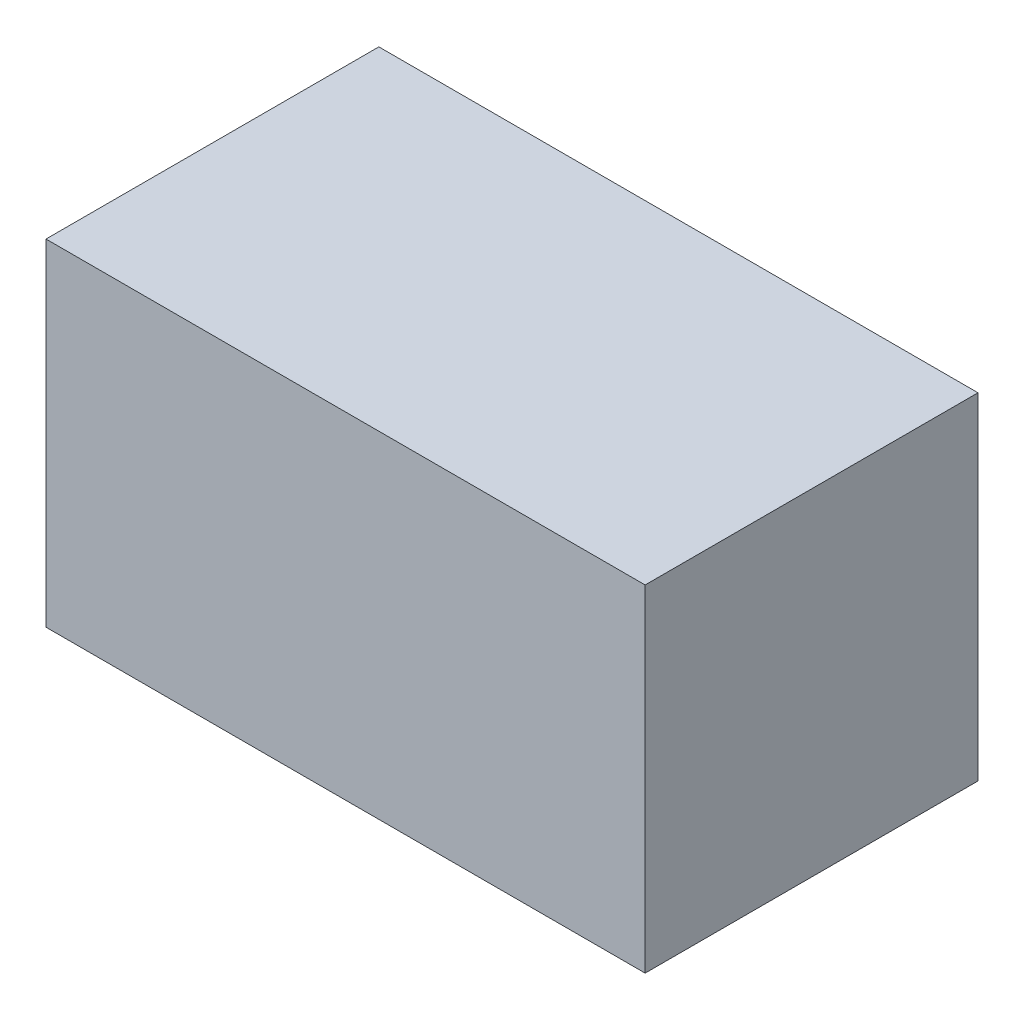
SolidWorks part; units mm, degrees
ref_plane "Front Plane" through (0, 0, 0) normal (0, 0, 1) x (1, 0, 0)
ref_plane "Top Plane" through (0, 0, 0) normal (0, 1, 0) x (1, 0, 0)
ref_plane "Right Plane" through (0, 0, 0) normal (1, 0, 0) x (0, 0, -1)
sketch "Sketch1" plane through (0, 0, 0) normal (0, 1, 0) x (1, 0, 0)
  line L1 (-27, -15) -> (27, -15)
  line L2 (-27, -15) -> (-27, 15)
  line L3 (-27, 15) -> (27, 15)
  line L4 (27, -15) -> (27, 15)
  point P6 (0, 15)
  point P7 (27, 0)
  dimension "D1" = 54
  dimension "D2" = 30
extrude "Boss-Extrude1" add sketch "Sketch1" along normal blind 30.3
sketch "Sketch2" plane through (0, 30.3, 0) normal (0, 1, 0) x (1, 0, 0)
  line L0 (-27, 15) -> (-27, -15) construction
  line L3 (0, 15) -> (0, -15) construction
  line L4 (27, 15) -> (-27, 15) construction
  line L5 (-27, -15) -> (27, -15) construction
  point P0 (21.2, 1.5)
  point P5 (-21.2, 1.5)
  dimension "D4" = 5.8
  dimension "D5" = 13.5
ref_axis "Axis1" through (-21.2, -9.3346, -1.5) along (0, 1, 0)
ref_axis "Axis2" through (21.2, -12.6712, -1.5) along (0, 1, 0)
